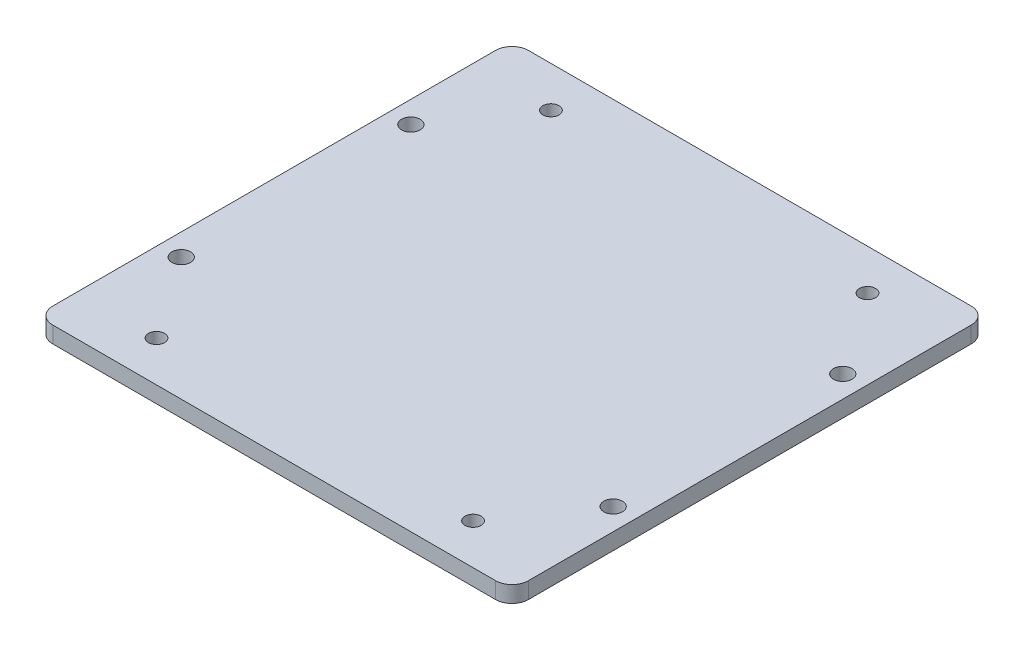
SolidWorks part; units mm, degrees
ref_plane "Front Plane" through (0, 0, 0) normal (0, 0, 1) x (1, 0, 0)
ref_plane "Top Plane" through (0, 0, 0) normal (0, 1, 0) x (1, 0, 0)
ref_plane "Right Plane" through (0, 0, 0) normal (1, 0, 0) x (0, 0, -1)
sketch "Sketch1" plane through (0, 0, 0) normal (0, 1, 0) x (1, 0, 0)
  line L0 (0, -43.5) -> (0, 43.5) construction
  line L1 (-40.5, 43.5) -> (40.5, 43.5)
  line L2 (-43.5, 40.5) -> (-43.5, -40.5)
  line L3 (-40.5, -43.5) -> (40.5, -43.5)
  line L4 (43.5, 40.5) -> (43.5, -40.5)
  line L5 (-43.5, 43.5) -> (43.5, -43.5) construction
  line L6 (-43.5, -43.5) -> (43.5, 43.5) construction
  line L7 (43.5, 0) -> (-43.5, 0) construction
  circle A0 centre (28.95, -36.07) radius 1.475
  circle A1 centre (28.95, 36.07) radius 1.475
  circle A2 centre (-28.95, 36.07) radius 1.475
  circle A3 centre (-28.95, -36.07) radius 1.475
  circle A4 centre (39.5, 21) radius 1.7
  circle A5 centre (-39.5, 21) radius 1.7
  circle A6 centre (39.5, -21) radius 1.7
  circle A7 centre (-39.5, -21) radius 1.7
  arc A9 (43.5, -40.5) -> (40.5, -43.5) centre (40.5, -40.5) cw
  arc A10 (-40.5, -43.5) -> (-43.5, -40.5) centre (-40.5, -40.5) cw
  arc A11 (-40.5, 43.5) -> (-43.5, 40.5) centre (-40.5, 40.5) ccw
  arc A12 (43.5, 40.5) -> (40.5, 43.5) centre (40.5, 40.5) ccw
  point P0 (0, 0)
  dimension "D5" = 2.95
  dimension "D8" = 3.4
  dimension "D9" = 3
  dimension "D1" = 87
  dimension "D2" = 87
  dimension "D3" = 36.07
  dimension "D4" = 28.95
  dimension "D6" = 21
  dimension "D7" = 39.5
extrude "Boss-Extrude1" add sketch "Sketch1" along normal blind 3
